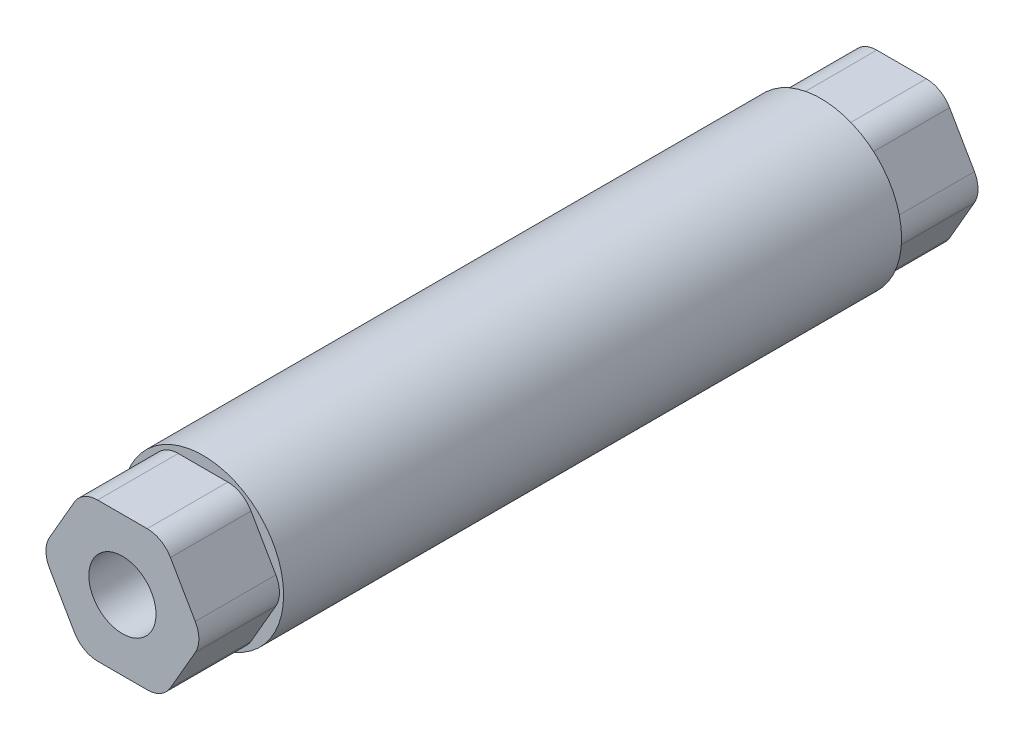
SolidWorks part; units mm, degrees
material "1060 Alloy"
ref_plane "Front Plane" through (0, 0, 0) normal (0, 0, 1) x (1, 0, 0)
ref_plane "Top Plane" through (0, 0, 0) normal (0, 1, 0) x (1, 0, 0)
ref_plane "Right Plane" through (0, 0, 0) normal (1, 0, 0) x (0, 0, -1)
sketch "Sketch1" plane through (0, 0, 0) normal (0, 0, 1) x (1, 0, 0)
  circle A0 centre (0, 0) radius 3
  dimension "D1" = 6
extrude "Boss-Extrude1" add sketch "Sketch1" along normal blind 29
ref_plane "Plane1" through (0, 0, 14.5) normal (0, 0, -1) x (-1, 0, 0)
sketch "Sketch3" plane through (0, 0, 29) normal (0, 0, 1) x (1, 0, 0)
  line L1 (3, 0) -> (1.5, 2.5981)
  line L2 (1.5, 2.5981) -> (-1.5, 2.5981)
  line L3 (-1.5, 2.5981) -> (-3, 0)
  line L4 (-3, 0) -> (-1.5, -2.5981)
  line L5 (-1.5, -2.5981) -> (1.5, -2.5981)
  line L6 (1.5, -2.5981) -> (3, 0)
  circle A0 centre (0, 0) radius 2.5981 construction
  circle M7 centre (0, 0) radius 3
extrude "Cut-Extrude1" cut sketch "Sketch3" against normal blind 3 contours L3 M7 | L1 M7 | L2 M7 | L4 M7 | L5 M7 | L6 M7 region at (2.3901, -1.3799, 29) region at (2.3901, 1.3799, 29) region at (0, 2.7598, 29) region at (0, -2.7598, 29) region at (-2.3901, 1.3799, 29) region at (-2.3901, -1.3799, 29)
mirror "Mirror1" about plane through (0, 0, 14.5) normal (0, 0, -1) of "Cut-Extrude1"
hole_wizard "Tap Drill for M3x0.5 Tap1" positions "Sketch4" profile "Sketch6" hole size "M3x0.5" standard "ANSI Metric"
sketch "Sketch4" plane through (0, 0, 29) normal (0, 0, 1) x (1, 0, 0)
  point P0 (0, 0)
sketch "Sketch6" plane through (0, 0, 29) normal (1, 0, 0) x (0, -1, 0)
  line L0 (0, 0) -> (0, 5.7511)
  line L1 (0, 5.7511) -> (1.25, 5)
  line L2 (1.25, 5) -> (1.25, 0)
  line L5 (1.25, 0) -> (0, 0)
  line L10 (0, 5.7511) -> (-1.25, 5) construction
  line L11 (0, -6.35) -> (0, 107.95) construction
  dimension "Hole Dia." = 2.5
  dimension "Hole Depth" = 5
  dimension "Drill Angle" = 118
mirror "Mirror2" about plane through (0, 0, 14.5) normal (0, 0, -1) of "Tap Drill for M3x0.5 Tap1"
fillet "Fillet1" radius 1 12 edges at (1.5, 2.5981, 1.5) (-1.5, 2.5981, 1.5) (-3, 0, 1.5) (-1.5, -2.5981, 1.5) (3, 0, 1.5) (1.5, -2.5981, 1.5) (-1.5, -2.5981, 27.5) (-3, 0, 27.5) (-1.5, 2.5981, 27.5) (1.5, 2.5981, 27.5) (3, 0, 27.5) (1.5, -2.5981, 27.5)
